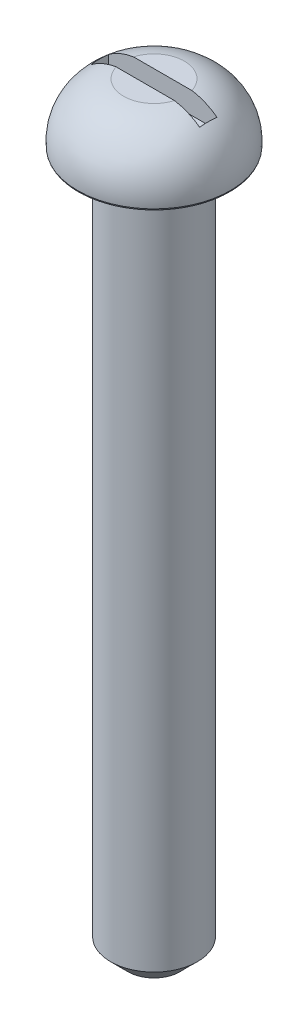
SolidWorks part; units mm, degrees
ref_plane "Спереди" through (0, 0, 0) normal (0, 0, 1) x (1, 0, 0)
ref_plane "Сверху" through (0, 0, 0) normal (0, 1, 0) x (1, 0, 0)
ref_plane "Справа" through (0, 0, 0) normal (1, 0, 0) x (0, 0, -1)
sketch "Эскиз1" plane through (0, 0, 0) normal (0, 0, 1) x (1, 0, 0)
  line L0 (3.5, 32.2) -> (2, 32.2)
  line L1 (0, 0) -> (0, 35)
  line L2 (2, 32.2) -> (2, 0.8)
  line L3 (2, 0.8) -> (1.2, 0)
  line L4 (1.2, 0) -> (0, 0)
  line L5 (0, 35) -> (1.4, 35)
  arc A0 (1.4, 35) -> (3.5, 32.2) centre (1, 32.5125) cw
  dimension "D2" = 1.4
  dimension "D8" = 1
  dimension "D1" = 35
  dimension "D3" = 2
  dimension "D4" = 1.2
  dimension "D5" = 2.8
  dimension "D6" = 3.5
  dimension "D7" = 45
revolve "Повернуть1" add sketch "Эскиз1" angle 360 about L1
fillet "Скругление1" radius 0.1 1 edges at (0, 32.2, -3.5)
sketch "Эскиз3" plane through (0, 35, 0) normal (0, 1, 0) x (-1, 0, 0)
  line L1 (2.5, -0.4) -> (-2.5, -0.4)
  line L2 (2.5, -0.4) -> (2.5, 0.4)
  line L3 (2.5, 0.4) -> (-2.5, 0.4)
  line L4 (-2.5, -0.4) -> (-2.5, 0.4)
  dimension "D1" = 0.8
  dimension "D2" = 0.4
  dimension "D3" = 5
  dimension "D4" = 2.5
extrude "Вырез-Вытянуть2" cut sketch "Эскиз3" against normal blind 1
ref_axis "Ось1" through (0, -9.8623, 0) along (0, 1, 0)
